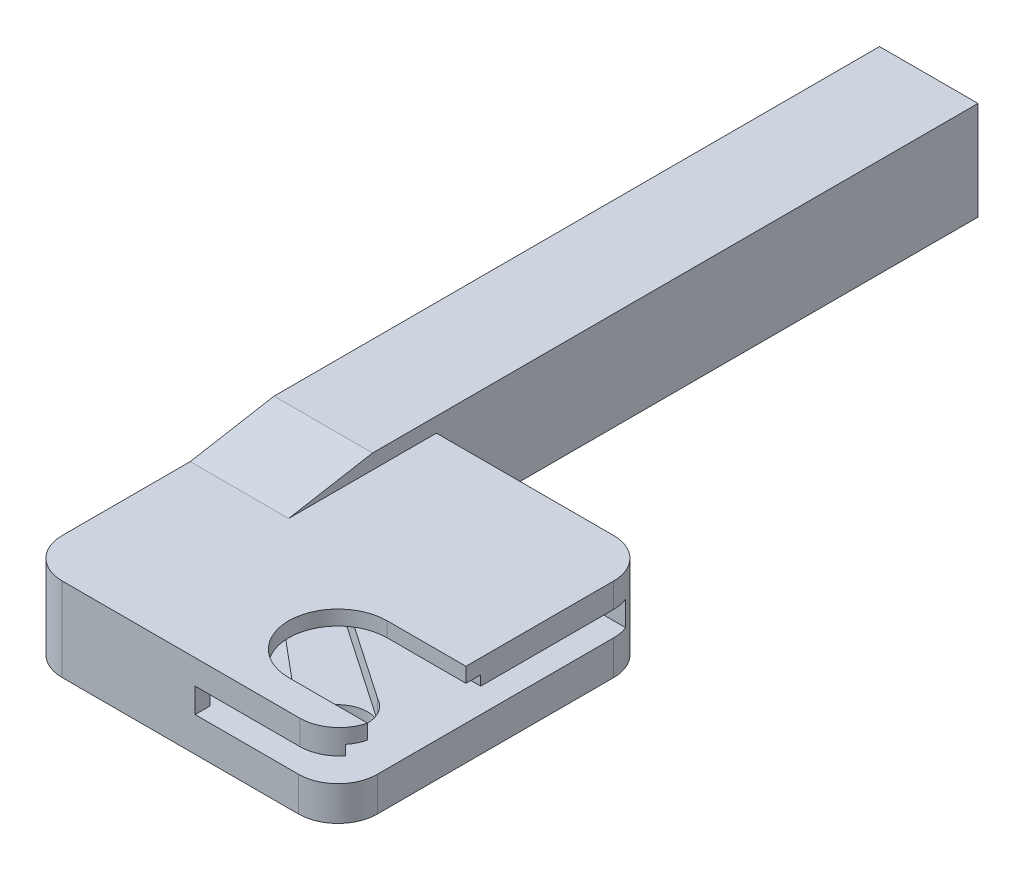
SolidWorks part; units mm, degrees
ref_plane "Front Plane" through (0, 0, 0) normal (0, 0, 1) x (1, 0, 0)
ref_plane "Top Plane" through (0, 0, 0) normal (0, 1, 0) x (1, 0, 0)
ref_plane "Right Plane" through (0, 0, 0) normal (1, 0, 0) x (0, 0, -1)
sketch "Sketch1" plane through (0, 0, 0) normal (0, 1, 0) x (1, 0, 0)
  line L0 (0, 0) -> (8, 0) construction
  line L1 (-24, 24) -> (8, 24)
  line L2 (-24, 24) -> (-24, -8)
  line L3 (-24, -8) -> (8, -8)
  line L4 (8, 24) -> (8, -8)
  line L5 (0, 0) -> (0, -8) construction
  dimension "D1" = 8
  dimension "D2" = 32
  dimension "D3" = 32
extrude "Block" add sketch "Sketch1" along normal blind 6.5 and the other way blind 2
sketch "Sketch2" plane through (0, 6.5, 0) normal (0, 1, 0) x (1, 0, 0)
  circle A0 centre (0, 0) radius 3
  dimension "D1" = 6
extrude "Center Hole" cut sketch "Sketch2" against normal through all
sketch "Sketch4" plane through (8, 0, -8) normal (-1, 0, 0) x (0, 0, 1)
  line L0 (8, 0) -> (8, 10) construction
  line L7 (14.5, 1.5) -> (1.5, 1.5)
  line L8 (14.5, 1.5) -> (14.5, 5)
  line L9 (14.5, 5) -> (1.5, 5)
  line L10 (1.5, 1.5) -> (1.5, 5)
  point P3 (8, 0)
  point P4 (8, 1.5)
  dimension "D2" = 3.5
  dimension "D4" = 13
extrude "Thick inside cut-out" cut sketch "Sketch4" along normal blind 30.5
sketch "Sketch5" plane through (8, 0, 0) normal (1, 0, 0) x (0, 0, -1)
  line L1 (6.5, 1.5) -> (21.5, 1.5)
  line L2 (6.5, 1.5) -> (6.5, 4)
  line L3 (6.5, 4) -> (21.5, 4)
  line L4 (21.5, 1.5) -> (21.5, 4)
  dimension "D1" = 15
  dimension "D2" = 2.5
extrude "Thin Cutout" cut sketch "Sketch5" against normal blind 14.5
fillet "Thick inside rounding" radius 6 2 edges at (-22.5, 3.25, -6.5) (-22.5, 3.25, 6.5)
fillet "Thin inside rounding" radius 6 1 edges at (-6.5, 2.75, -21.5)
sketch "Sketch6" plane through (8, 0, 0) normal (1, 0, 0) x (0, 0, -1)
  line L1 (6.5, 4) -> (-12.8454, 4)
  line L2 (6.5, 4) -> (6.5, 1.5)
  line L3 (6.5, 1.5) -> (-12.8454, 1.5)
  line L4 (-12.8454, 4) -> (-12.8454, 1.5)
extrude "TEMP Bottm Thin cut-out" cut sketch "Sketch6" against normal blind 14.5
sketch "Sketch7" plane through (0, 6.5, 0) normal (0, 1, 0) x (1, 0, 0)
  line L0 (0, 5) -> (8, 5)
  line L1 (8, -8) -> (8, 24) construction
  line L2 (8, 5) -> (8, -5)
  line L3 (8, -5) -> (0, -5)
  circle A0 centre (0, 0) radius 5 construction
  arc A1 (0, 5) -> (0, -5) centre (0, 0) ccw
  point P5 (0, 0)
extrude "Spline Hole" cut sketch "Sketch7" against normal up to next
sketch "Sketch8" plane through (0, 6.5, 0) normal (0, 1, 0) x (1, 0, 0)
  line L0 (8, 24) -> (-24, 24) construction
  line L1 (-24, 9) -> (-14, 9)
  line L2 (-24, 9) -> (-24, 79)
  line L3 (-24, 79) -> (-14, 79)
  line L4 (-14, 9) -> (-14, 79)
  point P5 (0, 0)
  point P6 (0, 0)
  dimension "D1" = 10
  dimension "D2" = 15
  dimension "D3" = 70
extrude "Pole" add sketch "Sketch8" along normal blind 1.5 and the other way blind 8.5
sketch "Sketch10" plane through (0, 0, -79) normal (0, 0, -1) x (-1, 0, 0)
  line L0 (14, 3) -> (24, 3) construction
  line L1 (14, -2) -> (14, 8) construction
  line L2 (24, -2) -> (24, 8) construction
  circle A0 centre (19, 3) radius 2.5
extrude "Pole Hole" cut sketch "Sketch10" against normal offset from surface (65 mm away) 10 up to face at (-3, 2.25, -24) offset beyond the face yes
chamfer "Chamfer3" distance 1.5 angle 80 1 edges at (-19, 8, -9) first distance on face at (-19, 7.25, -9)
sketch "Sketch11" plane through (0, 1.5, 0) normal (0, 1, 0) x (1, 0, 0)
  line L0 (0, 0) -> (-22.5, 0) construction
  line L1 (-22.5, 0.5) -> (-22.5, -0.5) construction
  circle A0 centre (-13.2, 0) radius 0.6
  circle A1 centre (-16.1, 0) radius 0.6
  circle A2 centre (-19, 0) radius 0.6
  circle A3 centre (-10.3, 0) radius 0.6
  dimension "D1" = 1.2
  dimension "D2" = 3.5
  dimension "D3" = 2.9
  dimension "D4" = 2.9
  dimension "D5" = 2.9
extrude "Inside Retainer Pins" add sketch "Sketch11" along normal blind 0.5
fillet "Retainer Pin Coning" radius 0.5 4 edges at (-10.3, 2, 0.6) (-13.2, 2, 0.6) (-16.1, 2, 0.6) (-19, 2, 0.6) conic rho 0.05
ref_plane "Wire Channel Plane" through (0, -0.5, 0) normal (0, -1, 0) x (-1, 0, 0)
sketch "Sketch12" plane through (0, -0.5, 0) normal (0, -1, 0) x (1, 0, 0)
  line L0 (-22.113, -14.5965) -> (-2.0007, 2.2355)
  line L1 (-2.0007, 2.2355) -> (2.0007, -2.2355)
  line L2 (2.0007, -2.2355) -> (-16.0544, -14.5965)
  line L3 (-16.0544, -14.5965) -> (-22.113, -14.5965)
  circle A0 centre (0, 0) radius 3 construction
  point P4 (-22.0036, -14.505)
  point P7 (-16.0544, -14.5965)
extrude "Wire Channel" cut sketch "Sketch12" against normal blind 4
fillet "Wire Channel Inside Round" radius 1 1 edges at (-18.9754, 3.5, -14) conic rho 0.05
fillet "Low Edge Rounding" radius 4 4 edges at (8, -0.25, 8) (8, 5.25, 8) (8, 2.25, -24) (-24, 2.25, 8)
sketch "Sketch13" plane through (-24, 0, 0) normal (-1, 0, 0) x (0, 0, 1)
  line L1 (-79.0589, 7) -> (-69.0589, 7)
  line L2 (-79.0589, 7) -> (-79.0589, -1)
  line L3 (-79.0589, -1) -> (-69.0589, -1)
  line L4 (-69.0589, 7) -> (-69.0589, -1)
  line L5 (-79, 8) -> (-17.5069, 8) construction
  line L6 (-79, -2) -> (4, -2) construction
  point P5 (-69.1668, 0.5721)
  point P6 (-69.0589, 5.4279)
  point P7 (0, 0)
  point P8 (0, 0)
  point P9 (0, 0)
  point P10 (0, 0)
  dimension "D1" = 10
  dimension "D2" = 1
  dimension "D3" = 1
extrude "Top Notch" cut sketch "Sketch13" against normal blind 7
